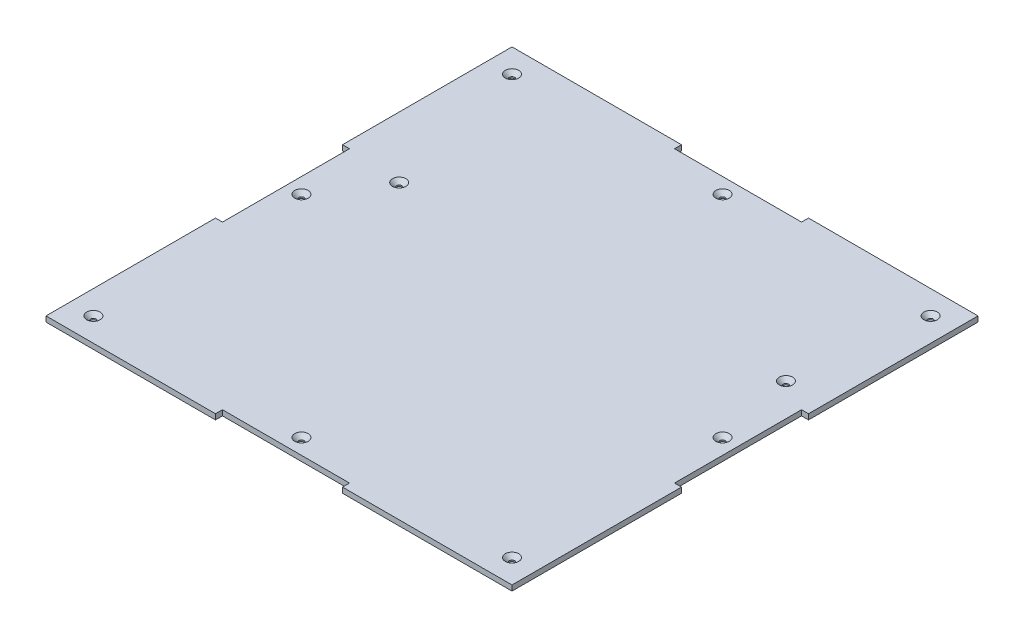
SolidWorks part; units mm, degrees
ref_plane "Front Plane" through (0, 0, 0) normal (0, 0, 1) x (1, 0, 0)
ref_plane "Top Plane" through (0, 0, 0) normal (0, 1, 0) x (1, 0, 0)
ref_plane "Right Plane" through (0, 0, 0) normal (1, 0, 0) x (0, 0, -1)
sketch "Sketch1" plane through (0, 0, 0) normal (0, 1, 0) x (1, 0, 0)
  line L0 (23.4, -87) -> (87, -87) construction
  line L1 (23.4, -84.4) -> (23.4, -87) construction
  line L2 (-23.4, -84.4) -> (23.4, -84.4) construction
  line L3 (-23.4, -87) -> (-23.4, -84.4) construction
  line L4 (-87, -87) -> (-23.4, -87) construction
  line L5 (-87, -23.4) -> (-87, -87) construction
  line L6 (-84.4, -23.4) -> (-87, -23.4) construction
  line L7 (-84.4, 23.4) -> (-84.4, -23.4) construction
  line L8 (-87, 23.4) -> (-84.4, 23.4) construction
  line L9 (-87, 87) -> (-87, 23.4) construction
  line L10 (-23.4, 87) -> (-87, 87) construction
  line L11 (-23.4, 84.4) -> (-23.4, 87) construction
  line L12 (23.4, 84.4) -> (-23.4, 84.4) construction
  line L13 (23.4, 87) -> (23.4, 84.4) construction
  line L14 (87, 87) -> (23.4, 87) construction
  line L15 (87, 23.4) -> (87, 87) construction
  line L16 (84.4, 23.4) -> (87, 23.4) construction
  line L17 (84.4, -23.4) -> (84.4, 23.4) construction
  line L18 (87, -23.4) -> (84.4, -23.4) construction
  line L19 (87, -87) -> (87, -23.4) construction
  line L20 (23.65, -86.75) -> (86.75, -86.75)
  line L21 (86.75, -86.75) -> (86.75, -23.65)
  line L22 (86.75, -23.65) -> (84.15, -23.65)
  line L23 (84.15, -23.65) -> (84.15, 23.65)
  line L24 (84.15, 23.65) -> (86.75, 23.65)
  line L25 (86.75, 23.65) -> (86.75, 86.75)
  line L26 (86.75, 86.75) -> (23.65, 86.75)
  line L27 (23.65, 86.75) -> (23.65, 84.15)
  line L28 (23.65, 84.15) -> (-23.65, 84.15)
  line L29 (-23.65, 84.15) -> (-23.65, 86.75)
  line L30 (-23.65, 86.75) -> (-86.75, 86.75)
  line L31 (-86.75, 86.75) -> (-86.75, 23.65)
  line L32 (-86.75, 23.65) -> (-84.15, 23.65)
  line L33 (-84.15, 23.65) -> (-84.15, -23.65)
  line L34 (-84.15, -23.65) -> (-86.75, -23.65)
  line L35 (-86.75, -23.65) -> (-86.75, -86.75)
  line L36 (-86.75, -86.75) -> (-23.65, -86.75)
  line L37 (-23.65, -86.75) -> (-23.65, -84.15)
  line L38 (-23.65, -84.15) -> (23.65, -84.15)
  line L39 (23.65, -84.15) -> (23.65, -86.75)
  point P20 (0, 84.4)
  point P22 (84.4, 0)
  dimension "D1" = 174
  dimension "D2" = 63.6
  dimension "D3" = 46.8
  dimension "D4" = 174
  dimension "D5" = 63.6
  dimension "D6" = 46.8
  dimension "D7" = 46.8
  dimension "D8" = 63.6
  dimension "D9" = 63.6
  dimension "D10" = 46.8
  dimension "D11" = 2.6
  dimension "D12" = 2.6
  dimension "D13" = 2.6
  dimension "D14" = 2.6
  dimension "D15" = 0.25
extrude "Boss-Extrude1" add sketch "Sketch1" along normal blind 2
sketch "Sketch2" plane through (0, 0, 0) normal (0, -1, 0) x (1, 0, 0)
  circle A0 centre (-77.9289, 77.9289) radius 1
  circle A1 centre (0, 78.4) radius 1
  circle A2 centre (77.9289, 77.9289) radius 1
  circle A3 centre (-78.4, 0) radius 1
  circle A4 centre (78.4, 0) radius 1
  circle A5 centre (72, -30) radius 1
  circle A6 centre (-64, -22) radius 1
  circle A7 centre (-77.9289, -77.9289) radius 1
  circle A8 centre (0, -78.4) radius 1
  circle A9 centre (77.9289, -77.9289) radius 1
  dimension "D1" = 2
  dimension "D2" = 2
  dimension "D3" = 2
  dimension "D4" = 2
  dimension "D5" = 2
  dimension "D6" = 2
  dimension "D7" = 2
  dimension "D8" = 2
  dimension "D9" = 2
  dimension "D10" = 2
extrude "Cut-Extrude1" cut sketch "Sketch2" against normal through all
chamfer "Chamfer1" distance 1.5 angle 45 10 edges at (-77.9289, 2, -78.9289) (0, 2, -79.4) (77.9289, 2, -78.9289) (72, 2, -31) (78.4, 2, -1) (-64, 2, -23) (-78.4, 2, -1) (-77.9289, 2, 76.9289) (0, 2, 77.4) (77.9289, 2, 76.9289)
